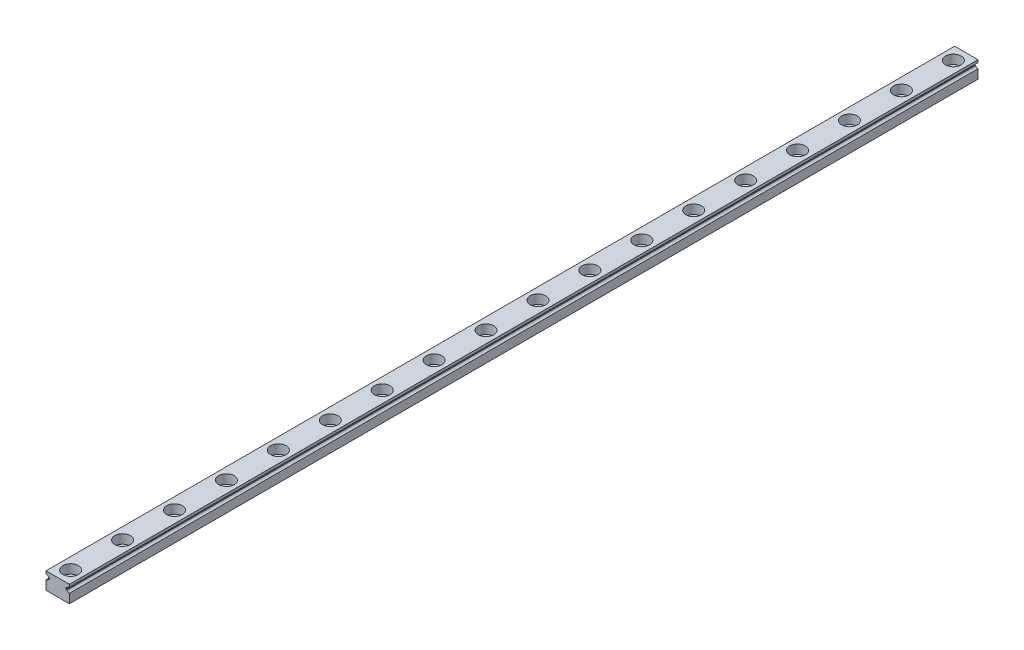
SolidWorks part; units mm, degrees
ref_plane "Спереди" through (0, 0, 0) normal (0, 0, 1) x (1, 0, 0)
ref_plane "Сверху" through (0, 0, 0) normal (0, 1, 0) x (1, 0, 0)
ref_plane "Справа" through (0, 0, 0) normal (1, 0, 0) x (0, 0, -1)
sketch "Sketch1" plane through (0, 0, 0) normal (0, 0, 1) x (1, 0, 0)
  line L0 (0, 0) -> (0, 5.7299) construction
  line L1 (-4.5, -3.25) -> (4.5, -3.25)
  line L2 (-4.5, -3.25) -> (-4.5, 0.25)
  line L3 (-4.5, 3.25) -> (4.5, 3.25)
  line L4 (4.5, -3.25) -> (4.5, 0.25)
  line L5 (-4.5, -3.25) -> (4.5, 3.25) construction
  line L6 (-4.5, 3.25) -> (4.5, -3.25) construction
  line L7 (-4.5, 2.25) -> (-4.5, 3.25)
  line L8 (-3.564, 0.898) -> (-3.2351, 0.898)
  line L9 (3.564, 0.898) -> (3.2351, 0.898)
  line L10 (-3.564, 1.602) -> (-3.2351, 1.602)
  line L11 (-3.2351, 0.898) -> (-3.2351, 1.602)
  line L12 (3.2351, 0.898) -> (3.2351, 1.602)
  line L13 (3.564, 1.602) -> (3.2351, 1.602)
  line L14 (4.5, 2.25) -> (4.5, 3.25)
  arc A0 (-3.564, 1.602) -> (-4.5, 2.25) centre (-4.5, 1.25) ccw
  arc A1 (-4.5, 0.25) -> (-3.564, 0.898) centre (-4.5, 1.25) ccw
  arc A2 (4.5, 0.25) -> (3.564, 0.898) centre (4.5, 1.25) cw
  arc A3 (3.564, 1.602) -> (4.5, 2.25) centre (4.5, 1.25) cw
  point P0 (0, 0)
  dimension "D3" = 1
  dimension "D1" = 9
  dimension "D2" = 6.5
  dimension "D4" = 2
extrude "Extrude1" add sketch "Sketch1" along normal blind 350
sketch "Sketch2" plane through (0, 3.25, 0) normal (0, 1, 0) x (1, 0, 0)
  line L0 (4.5, 0) -> (-4.5, 0) construction
  circle A0 centre (0, -5) radius 1.75
  circle A1 centre (0, -5) radius 3
  dimension "D1" = 3.5
  dimension "D2" = 6
  dimension "D3" = 5
extrude "Extrude2" cut sketch "Sketch2" against normal blind 3.5 contours A1
extrude "Extrude3" cut sketch "Sketch" against normal through all contours A0
sketch "Sketch" plane through (0, 3.25, 0) normal (0, 1, 0) x (1, 0, 0) same geometry as "Sketch2"
pattern_linear "LPattern1" count 18 spacing 20 along (0, 0, 1) of "Extrude2", "Extrude3"
